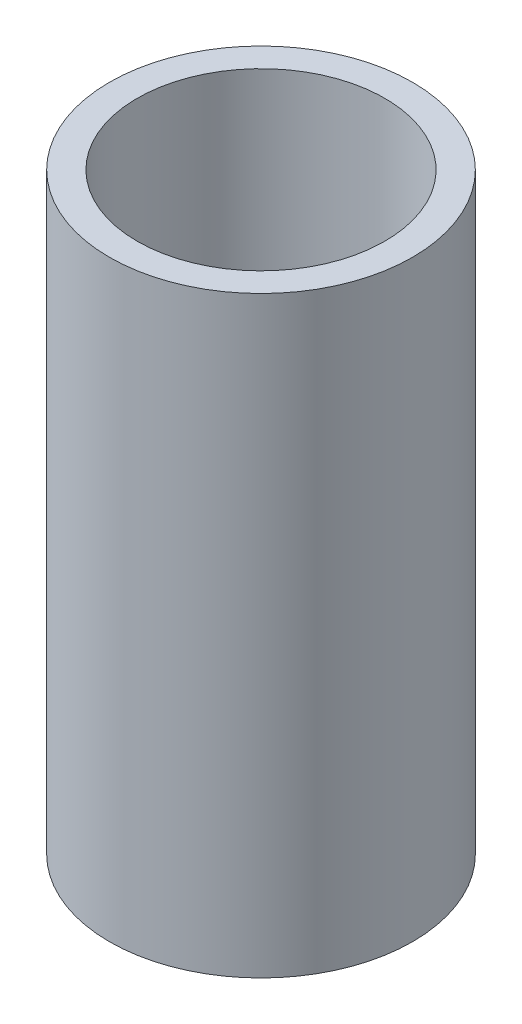
SolidWorks part; units mm, degrees
ref_plane "Front Plane" through (0, 0, 0) normal (0, 0, 1) x (1, 0, 0)
ref_plane "Top Plane" through (0, 0, 0) normal (0, 1, 0) x (1, 0, 0)
ref_plane "Right Plane" through (0, 0, 0) normal (1, 0, 0) x (0, 0, -1)
sketch "Sketch1" plane through (0, 0, 0) normal (0, 1, 0) x (1, 0, 0)
  circle A0 centre (0, 0) radius 20
  dimension "SLEEVE_OD" = 40
extrude "Boss-Extrude1" add sketch "Sketch1" along normal blind 78.2167
sketch "Sketch2" plane through (0, 0, 0) normal (0, 1, 0) x (1, 0, 0)
  circle A0 centre (0, 0) radius 16.3382
  dimension "BORE_D" = 32.6764
extrude "Cut-Extrude1" cut sketch "Sketch2" along normal through all
chamfer "Chamfer1" distance 3.8452 angle 45 rebuild error yes
